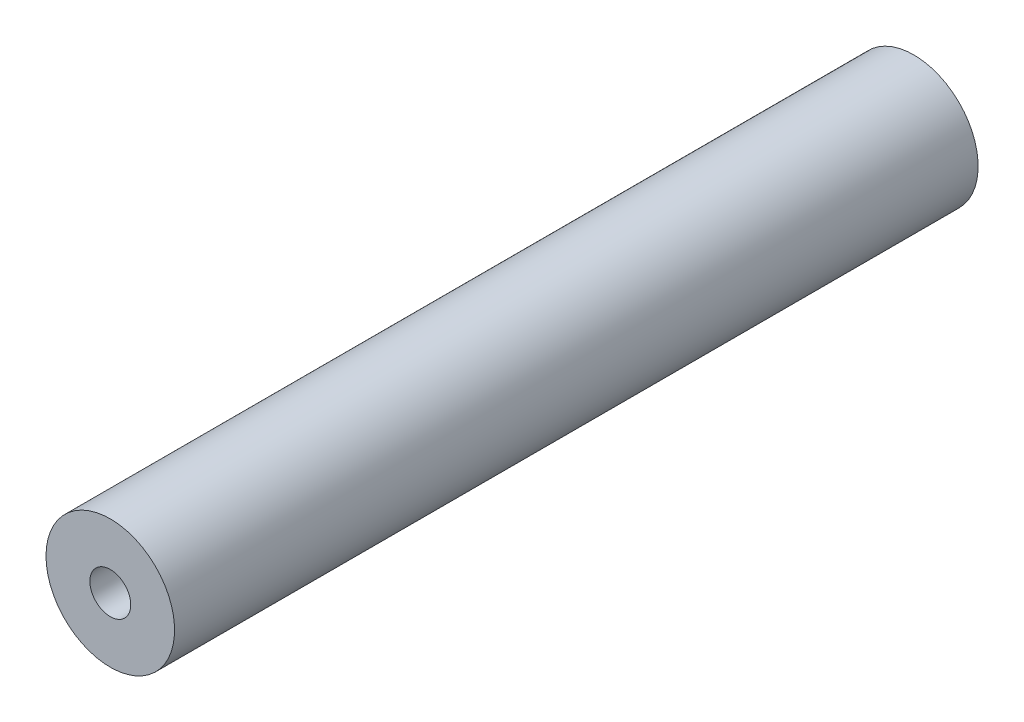
SolidWorks part; units mm, degrees
material "6061-T6 (SS)"
ref_plane "Front Plane" through (0, 0, 0) normal (0, 0, 1) x (1, 0, 0)
ref_plane "Top Plane" through (0, 0, 0) normal (0, 1, 0) x (1, 0, 0)
ref_plane "Right Plane" through (0, 0, 0) normal (1, 0, 0) x (0, 0, -1)
sketch "Sketch1" plane through (0, 0, 0) normal (0, 0, 1) x (1, 0, 0)
  circle A1 centre (0, 0) radius 6.35
  dimension "D2" = 12.7
extrude "Boss-Extrude1" add sketch "Sketch1" along normal mid plane 79.375 contours A1 region at (0, 0, 0)
hole_wizard "#10-32 Tapped Hole1" positions "3DSketch1" profile "Sketch2" tap size "#10-32" standard "ANSI Inch"
sketch3d "3DSketch1"
  line L0 (0, 0, 39.6875) -> (0, 0, -39.6875) construction
  point P0 (0, 0, -39.6875)
  point P4 (0, 0, 39.6875)
sketch "Sketch2" plane through (0, 0, -39.6875) normal (1, 0, 0) x (0, 1, 0)
  line L0 (0, 0) -> (0, 13.2428)
  line L1 (0, 13.2428) -> (2.0193, 12.0294)
  line L2 (2.0193, 12.0294) -> (2.0193, 0)
  line L5 (2.0193, 0) -> (0, 0)
  line L10 (0, 13.2428) -> (-2.0193, 12.0294) construction
  line L11 (0, -6.35) -> (0, 107.95) construction
  dimension "Tap Drill Dia." = 4.0386
  dimension "Tap Drill Depth" = 12.0294
  dimension "Drill Angle" = 118
cosmetic thread "Hole Thread1"
cosmetic thread "Hole Thread2"
